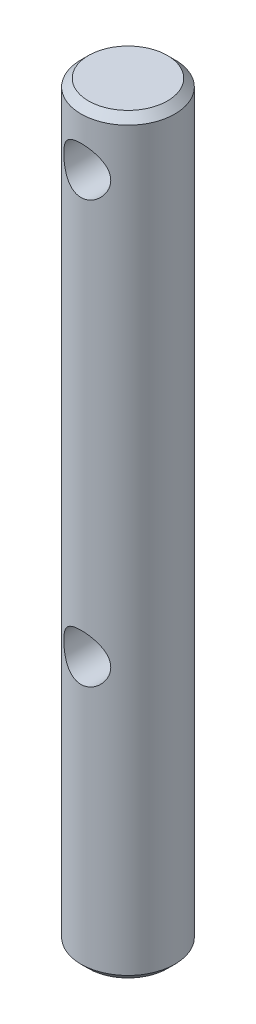
SolidWorks part; units mm, degrees
material "6061-T6 (SS)"
ref_plane "Front Plane" through (0, 0, 0) normal (0, 0, 1) x (1, 0, 0)
ref_plane "Top Plane" through (0, 0, 0) normal (0, 1, 0) x (1, 0, 0)
ref_plane "Right Plane" through (0, 0, 0) normal (1, 0, 0) x (0, 0, -1)
sketch "Sketch1" plane through (0, 0, 0) normal (0, 1, 0) x (1, 0, 0)
  circle A0 centre (0, 0) radius 3.175
  dimension "D1" = 6.35
extrude "Boss-Extrude1" add sketch "Sketch1" along normal blind 50.8
chamfer "Chamfer1" distance 0.508 angle 45 2 edges at (0, 0, 3.175) (0, 50.8, 3.175)
sketch "Sketch2" plane through (0, 0, 0) normal (0, 0, 1) x (1, 0, 0)
  line L0 (-15.9932, 15.875) -> (12.4307, 15.875)
  line L1 (-14.932, 0) -> (13.9466, 0)
  line L2 (-15.9932, 16.891) -> (12.4307, 16.891)
  line L3 (-15.9932, 39.116) -> (15.3868, 39.116)
  line L4 (-15.9932, 40.132) -> (15.3868, 40.132)
  line L5 (2.667, 50.8) -> (-2.667, 50.8) construction
  line L6 (3.175, 0.508) -> (3.175, 50.292) construction
  circle A0 centre (0, 46.99) radius 1.5875
  circle A1 centre (0, 18.4785) radius 1.5875
  dimension "D5" = 3.175
  dimension "D8" = 3.175
  dimension "D1" = 15.875
  dimension "D2" = 1.016
  dimension "D3" = 22.225
  dimension "D4" = 1.016
  dimension "D6" = 3.81
  dimension "D7" = 3.175
extrude "Cut-Extrude1" cut sketch "Sketch2" along normal blind 50.8 and the other way blind 50.8 contours A0 | A1
